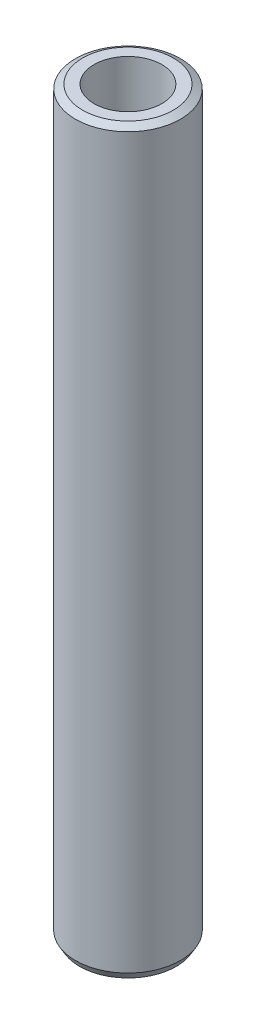
SolidWorks part; units mm, degrees
ref_plane "Front Plane" through (0, 0, 0) normal (0, 0, 1) x (1, 0, 0)
ref_plane "Top Plane" through (0, 0, 0) normal (0, 1, 0) x (1, 0, 0)
ref_plane "Right Plane" through (0, 0, 0) normal (1, 0, 0) x (0, 0, -1)
sketch "Sketch1" plane through (0, 0, 0) normal (0, 1, 0) x (1, 0, 0)
  circle A0 centre (0, 0) radius 20
  dimension "SHAFT_OD" = 40
extrude "Boss-Extrude1" add sketch "Sketch1" along normal blind 281.6996
sketch "Sketch2" plane through (0, 0, 0) normal (0, 1, 0) x (1, 0, 0)
  circle A0 centre (0, 0) radius 12.9081
  dimension "BORE_D" = 25.8161
extrude "Cut-Extrude1" cut sketch "Sketch2" along normal through all
chamfer "Chamfer1" distance 1.5851 angle 60 2 edges at (0, 281.6996, 20) (0, 0, 20) first distance on face at (0, 281.6996, 20) first distance on face at (0, 0, 12.9081)
